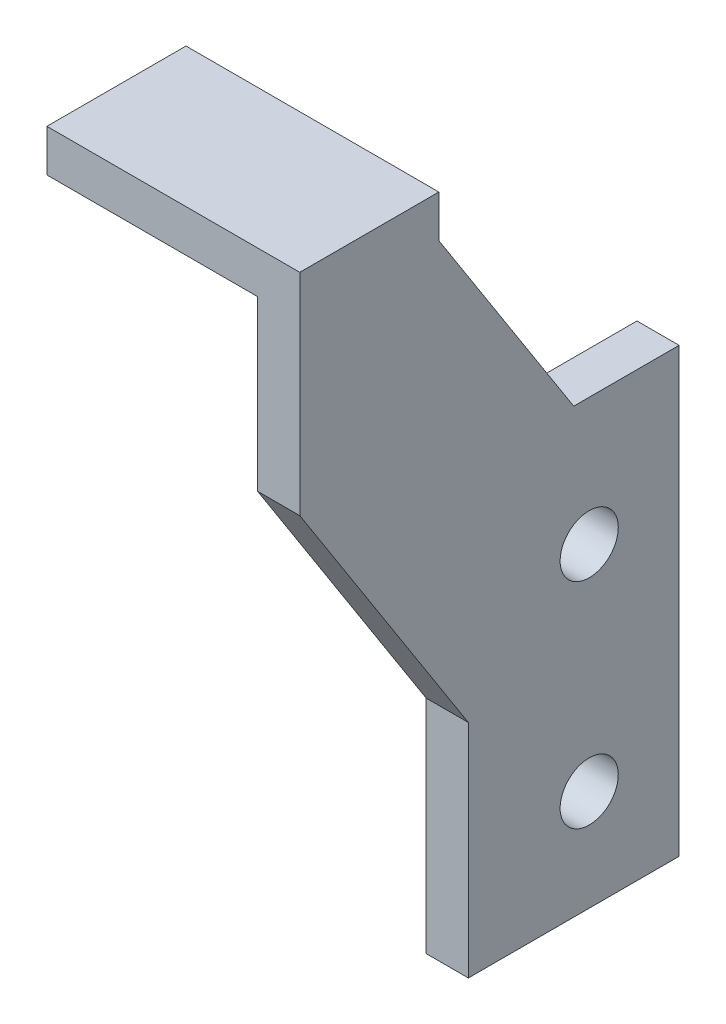
SolidWorks part; units mm, degrees
ref_plane "Front" through (0, 0, 0) normal (0, 0, 1) x (1, 0, 0)
ref_plane "Top" through (0, 0, 0) normal (0, 1, 0) x (1, 0, 0)
ref_plane "Right" through (0, 0, 0) normal (1, 0, 0) x (0, 0, -1)
ref_plane "Plane1" through (-334.0461, 0, 0) normal (-1, 0, 0) x (0, 0, 1)
sketch "Sketch1" plane through (-334.0461, 0, 0) normal (-1, 0, 0) x (0, 0, 1)
  line L0 (-720.2969, -311.4178) -> (-720.2969, -285.1678) construction
  line L1 (-723.9662, -285.1678) -> (-720.2969, -285.1678) construction
  line L2 (-723.9662, -285.1678) -> (-723.9662, -271.3698) construction
  line L3 (-723.9662, -271.3698) -> (-723.9662, -244.1178) construction
  line L4 (-723.9662, -244.1178) -> (-745.2969, -244.1178) construction
  line L5 (-745.2969, -340.8678) -> (-723.9662, -340.8678) construction
  line L6 (-723.9662, -340.8678) -> (-723.9662, -285.1678) construction
  line L7 (-745.2969, -244.1178) -> (-745.2969, -340.8678) construction
  line L8 (-734.6315, -262.1678) -> (-734.6315, -340.8678) construction
  line L9 (-716.7969, -260.1678) -> (-700.2969, -260.1678)
  line L10 (-745.2969, -337.6678) -> (-720.2969, -337.6678)
  line L11 (-745.2969, -337.6678) -> (-745.2969, -285.1678)
  line L12 (-745.2969, -285.1678) -> (-732.7969, -285.1678)
  line L13 (-720.2969, -337.6678) -> (-720.2969, -311.4178)
  line L14 (-700.2969, -260.1678) -> (-700.2969, -280.1678)
  line L15 (-700.2969, -280.1678) -> (-720.2969, -311.4178)
  line L16 (-716.7969, -260.1678) -> (-732.7969, -285.1678)
  line L17 (-732.7969, -285.1678) -> (-723.9662, -285.1678) construction
  circle A3 centre (-734.6315, -262.1678) radius 3.45 construction
  circle A4 centre (-734.6315, -325.6678) radius 3.45
  circle A5 centre (-734.6315, -300.2678) radius 3.45
  point P17 (-701.5077, -261.916)
  point P21 (-689.1862, -260.9174)
  point P22 (-706.761, -262.8346)
  point P23 (-689.2969, -281.0486)
  point P24 (-689.2969, -260.1678)
  point P27 (0, 0)
  dimension "D1" = 6.9
  dimension "D2" = 6.9
  dimension "D3" = 38.1
  dimension "D4" = 25.4
  dimension "D5" = 25
  dimension "D6" = 12
  dimension "D8" = 45
  dimension "D7" = 23
  dimension "D9" = 25
  dimension "D10" = 20
  dimension "D11" = 31.25
  dimension "D12" = 12.5
extrude "Boss-Extrude1" add sketch "Sketch1" along normal blind 5
sketch "Sketch2" plane through (0, 0, -700.2969) normal (0, 0, 1) x (1, 0, 0)
  line L0 (-334.0461, -260.1678) -> (-364.0461, -260.1678)
  line L1 (-334.0461, -280.1678) -> (-334.0461, -260.1678) construction
  line L2 (-339.0461, -260.1678) -> (-334.0461, -260.1678) construction
  dimension "D1" = 30
extrude "Extrude-Thin1" add sketch "Sketch2" against normal blind 16.5 thin thin type one direction wall 5
equation "\"D2@Sketch1\"=\"D1@Sketch1\""
equation "\"D12@Sketch1\"=\"D5@Sketch1\"/2"
